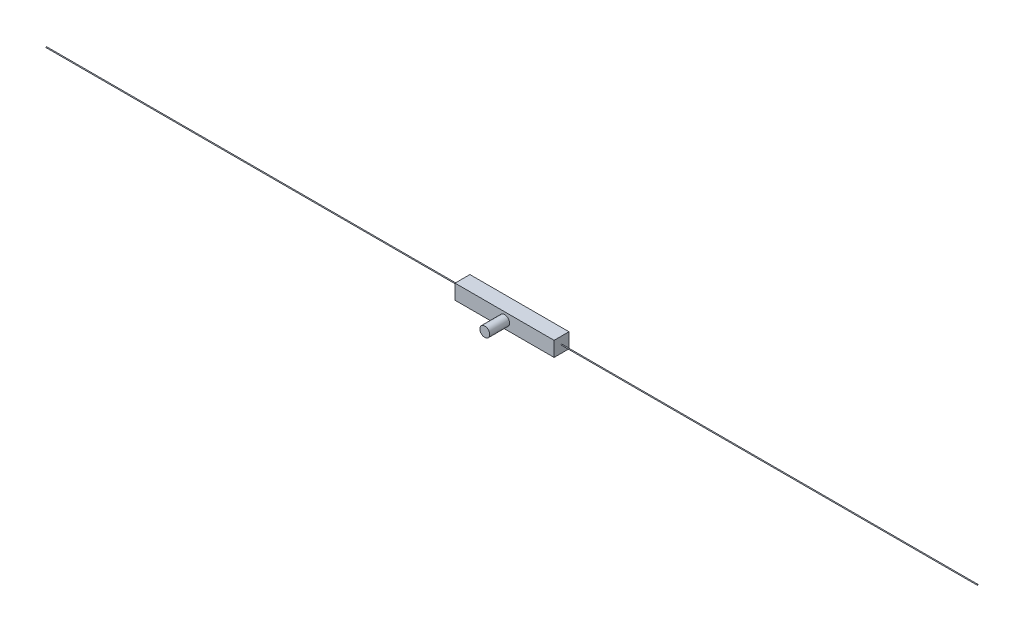
SolidWorks part; units mm, degrees
ref_plane "Front Plane" through (0, 0, 0) normal (0, 0, 1) x (1, 0, 0)
ref_plane "Top Plane" through (0, 0, 0) normal (0, 1, 0) x (1, 0, 0)
ref_plane "Right Plane" through (0, 0, 0) normal (1, 0, 0) x (0, 0, -1)
sketch "Sketch1" plane through (0, 0, 0) normal (0, 0, 1) x (1, 0, 0)
  line L1 (0, 0) -> (100, 0)
  line L2 (0, 0) -> (0, 15)
  line L3 (0, 15) -> (100, 15)
  line L4 (100, 0) -> (100, 15)
  circle A0 centre (50, 7.5) radius 5
  dimension "D1" = 10
  dimension "D2" = 15
  dimension "D3" = 7.5
  dimension "D4" = 50
  dimension "D5" = 100
extrude "Boss-Extrude1" add sketch "Sketch1" along normal blind 15
extrude "Boss-Extrude2" add sketch "Sketch1<2>" along normal blind 35 contours A0 region at (50, 7.5, 0)
sketch "Sketch1<2>" plane through (0, 0, 0) normal (0, 0, 1) x (1, 0, 0) same geometry as "Sketch1"
sketch "Sketch2" plane through (0, 0, 0) normal (-1, 0, 0) x (0, 0, 1)
  line L0 (0, 15) -> (0, 0) construction
  line L1 (15, 0) -> (0, 0) construction
  circle A0 centre (7.5, 7.5) radius 0.4064
  dimension "D3" = 0.8128
  dimension "D1" = 7.5
  dimension "D2" = 7.5
extrude "Boss-Extrude3" add sketch "Sketch2" along normal blind 420
extrude "Boss-Extrude4" add sketch "Sketch2<2>" against normal blind 520
sketch "Sketch2<2>" plane through (0, 0, 0) normal (-1, 0, 0) x (0, 0, 1) same geometry as "Sketch2"
